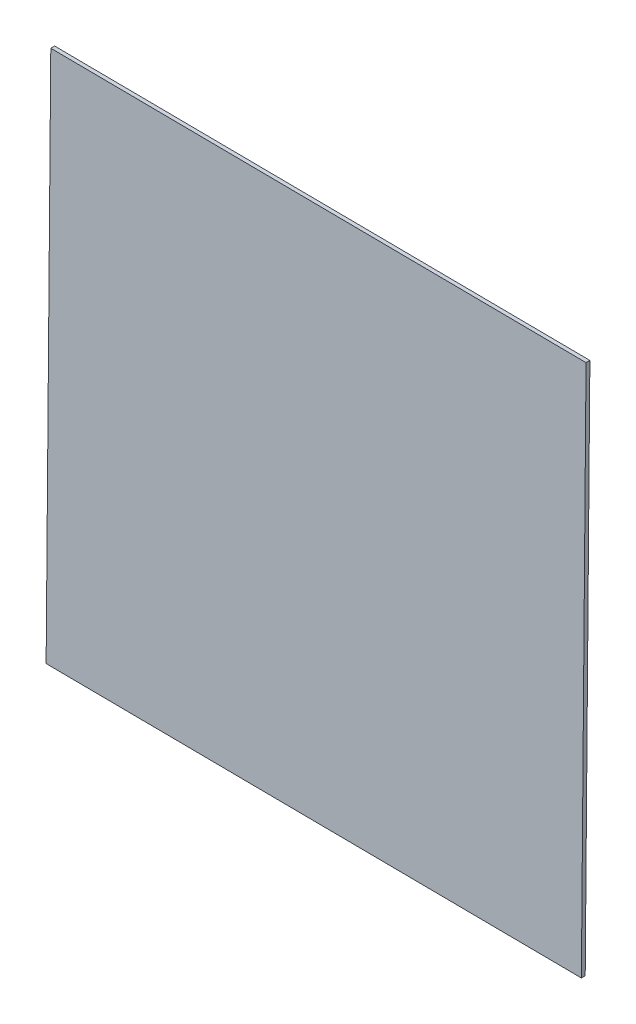
SolidWorks part; units mm, degrees
ref_plane "Front Plane" through (0, 0, 0) normal (0, 0, 1) x (1, 0, 0)
ref_plane "Top Plane" through (0, 0, 0) normal (0, 1, 0) x (1, 0, 0)
ref_plane "Right Plane" through (0, 0, 0) normal (1, 0, 0) x (0, 0, -1)
sketch "Sketch1" plane through (0, 0, 0) normal (0, 0, 1) x (1, 0, 0)
  line L4 (-97.7146, 56.2371) -> (-79.9861, 56.0824)
  line L5 (-79.9861, 56.0824) -> (-79.8314, 73.8109)
  line L6 (-79.8314, 73.8109) -> (-97.5599, 73.9656)
  line L7 (-97.5599, 73.9656) -> (-97.7146, 56.2371)
  line L8 (-97.7146, 56.2371) -> (-79.9861, 56.0824)
  line L9 (-79.9861, 56.0824) -> (-79.8314, 73.8109)
  line L10 (-79.8314, 73.8109) -> (-97.5599, 73.9656)
  line L11 (-97.5599, 73.9656) -> (-97.7146, 56.2371)
  dimension "D1" = 0
extrude "Boss-Extrude1" add sketch "Sketch1" along normal blind 0.127
sketch "Sketch2" plane through (0, 0, 0) normal (0, 0, -1) x (-1, 0, 0)
  line L0 (97.6376, 65.024) -> (79.9084, 65.024) construction
  line L1 (79.9861, 56.0824) -> (79.8314, 73.8109) construction
  line L2 (97.5599, 73.9656) -> (97.7146, 56.2371) construction
  line L3 (79.9084, 57.1754) -> (97.6376, 57.1754) construction
  line L4 (79.9328, 62.1919) -> (97.6627, 62.1919) construction
  line L7 (86.233, 57.1754) -> (89.1133, 57.1754)
  line L8 (89.1133, 57.1754) -> (91.313, 60.9854)
  line L9 (91.313, 60.9854) -> (88.4327, 60.9854)
  line L10 (88.4327, 60.9854) -> (86.233, 57.1754)
  line L11 (88.773, 73.8886) -> (88.773, 56.1594) construction
  line L14 (81.4477, 57.1754) -> (84.328, 57.1754)
  line L15 (84.328, 57.1754) -> (86.5277, 60.9854)
  line L16 (86.5277, 60.9854) -> (83.6474, 60.9854)
  line L17 (83.6474, 60.9854) -> (81.4477, 57.1754)
  line L18 (91.0183, 57.1754) -> (93.218, 60.9854)
  line L19 (93.218, 60.9854) -> (96.0983, 60.9854)
  line L20 (96.0983, 60.9854) -> (93.8986, 57.1754)
  line L21 (93.8986, 57.1754) -> (91.0183, 57.1754)
  line L22 (79.9084, 72.8726) -> (97.6376, 72.8726) construction
  line L23 (86.233, 69.0626) -> (89.1133, 69.0626)
  line L24 (89.1133, 69.0626) -> (91.313, 72.8726)
  line L25 (91.313, 72.8726) -> (88.4327, 72.8726)
  line L26 (88.4327, 72.8726) -> (86.233, 69.0626)
  line L27 (81.4477, 69.0626) -> (84.328, 69.0626)
  line L28 (84.328, 69.0626) -> (86.5277, 72.8726)
  line L29 (86.5277, 72.8726) -> (83.6474, 72.8726)
  line L30 (83.6474, 72.8726) -> (81.4477, 69.0626)
  line L31 (91.0183, 69.0626) -> (93.218, 72.8726)
  line L32 (93.218, 72.8726) -> (96.0983, 72.8726)
  line L33 (96.0983, 72.8726) -> (93.8986, 69.0626)
  line L34 (93.8986, 69.0626) -> (91.0183, 69.0626)
  line L35 (87.6731, 57.1754) -> (89.8729, 60.9854) construction
  text T0 "<b>FIRE</b>" font "GordonURWMed" height in points 24
  point P18 (87.6731, 57.1754)
  point P26 (89.8729, 60.9854)
  point P40 (87.6731, 69.0626)
  point P43 (89.8729, 72.8726)
  point P53 (88.773, 59.0804)
  dimension "D1" = 2.8321
wrap "FIRE" sketch "Sketch2" wrap type scribe source sketch "Sketch2" face at (-88.773, 65.024, 0)
sketch "Sketch3" [suppressed] plane through (0, 0, 0) normal (0, 0, -1) x (-1, 0, 0)
  line L0 (79.9084, 65.3056) -> (97.6376, 65.3056) construction
  line L3 (79.9084, 65.024) -> (97.6376, 65.024) construction
  line L4 (79.9084, 60.5059) -> (97.6376, 60.5059) construction
  line L5 (79.9084, 69.5421) -> (97.6376, 69.5421) construction
  line L6 (95.8049, 69.5421) -> (95.8049, 60.5059) construction
  text T0 "APU" font "GordonURWMed" height in points 18
  text T1 "FIRE" font "GordonURWMed" height in points 18
  point P15 (95.8049, 65.024)
wrap "APU FIRE" [suppressed] sketch "Sketch3" source sketch "Sketch3"
sketch "Sketch4" [suppressed] plane through (0, 0, 0) normal (0, 0, -1) x (-1, 0, 0)
  line L0 (79.9084, 65.4564) -> (97.6376, 65.4564) construction
  line L4 (79.9084, 65.024) -> (97.6376, 65.024) construction
  line L6 (79.9084, 61.4926) -> (97.6376, 61.4926) construction
  text T0 "MASTER" font "GordonURWCon" height in points 14
  text T1 "CAUTION" font "GordonURWCon" height in points 14
wrap "MC" [suppressed] sketch "Sketch4" source sketch "Sketch4"
